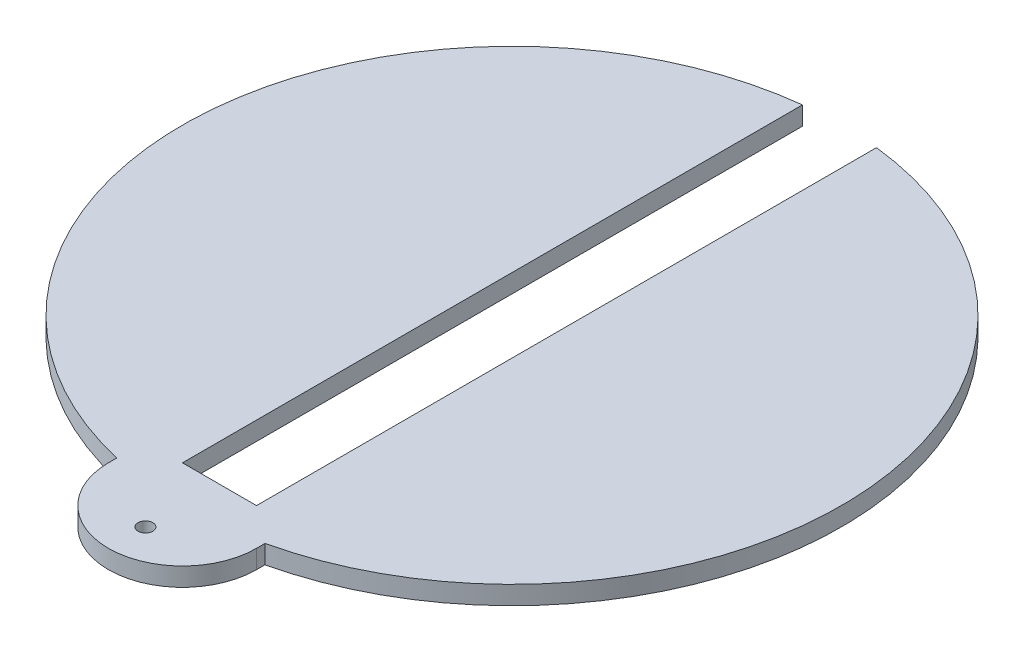
SolidWorks part; units mm, degrees
ref_plane "Front Plane" through (0, 0, 0) normal (0, 0, 1) x (1, 0, 0)
ref_plane "Top Plane" through (0, 0, 0) normal (0, 1, 0) x (1, 0, 0)
ref_plane "Right Plane" through (0, 0, 0) normal (1, 0, 0) x (0, 0, -1)
sketch "Sketch2" plane through (0, 0, 0) normal (0, 1, 0) x (1, 0, 0)
  line L0 (6.35, 56.515) -> (56.515, 56.515)
  line L1 (-56.515, -56.515) -> (-12.7, -56.515)
  line L2 (-56.515, -56.515) -> (-56.515, 56.515)
  line L3 (-56.515, 56.515) -> (-6.35, 56.515)
  line L4 (56.515, -56.515) -> (56.515, 56.515)
  line L5 (-56.515, -56.515) -> (56.515, 56.515) construction
  line L6 (-56.515, 56.515) -> (56.515, -56.515) construction
  line L7 (-6.35, -50.165) -> (6.35, -50.165)
  line L8 (-6.35, -50.165) -> (-6.35, 56.515)
  line L10 (6.35, -50.165) -> (6.35, 56.515)
  line L11 (-6.35, -50.165) -> (6.35, 56.515) construction
  line L12 (-6.35, 56.515) -> (6.35, -50.165) construction
  line L13 (12.7, -56.515) -> (56.515, -56.515)
  arc A0 (-12.7, -56.515) -> (12.7, -56.515) centre (0, -56.515) ccw
  point P0 (0, 0)
  point P6 (0, 3.175)
  dimension "D5" = 12.7
  dimension "D1" = 113.03
  dimension "D2" = 113.03
  dimension "D3" = 12.7
  dimension "D4" = 106.68
extrude "Boss-Extrude1" add sketch "Sketch2" along normal blind 3.175 contours L3 L8 L7 L10 L0 L4 L13 A0 L1 L2
sketch "Sketch3" plane through (0, 3.175, 0) normal (0, 1, 0) x (1, 0, 0)
  line L1 (-6.35, -50.165) -> (6.35, -50.165) construction
  circle A0 centre (0, -62.865) radius 1.27
  dimension "D1" = 2.54
  dimension "D2" = 12.7
extrude "Cut-Extrude1" cut sketch "Sketch3" against normal through all
sketch "Sketch4" plane through (0, 3.175, 0) normal (0, 1, 0) x (1, 0, 0)
  line L0 (-56.515, 56.515) -> (56.515, 56.515)
  line L1 (56.515, 56.515) -> (56.515, -56.515)
  line L3 (56.515, -56.515) -> (12.7, -56.515)
  line L4 (12.7, -56.515) -> (12.7, -55.0695)
  line L5 (-12.7, -55.0695) -> (-12.7, -56.515)
  line L6 (-12.7, -56.515) -> (-56.515, -56.515)
  line L7 (-56.515, -56.515) -> (-56.515, 56.515)
  arc A5 (12.7, -55.0695) -> (-12.7, -55.0695) centre (0, 0) ccw
  line M11 (-56.515, 56.515) -> (-56.515, -56.515)
  line M12 (-56.515, -56.515) -> (-12.7, -56.515)
  line M14 (12.7, -56.515) -> (56.515, -56.515)
  line M15 (56.515, -56.515) -> (56.515, 56.515)
  line M16 (56.515, 56.515) -> (6.35, 56.515)
  line M17 (6.35, 56.515) -> (6.35, -50.165)
  line M19 (-6.35, -50.165) -> (-6.35, 56.515)
  line M20 (-6.35, 56.515) -> (-56.515, 56.515)
extrude "Cut-Extrude2" cut sketch "Sketch4" against normal through all both and the other way through all contours M11 M12 | M19 M20 M11 | M14 M15 | M15 M16 M17 region at (44.1992, 3.175, 43.7821) region at (-44.1992, 3.175, 43.7821) region at (-43.9346, 3.175, -43.8775) region at (43.9346, 3.175, -43.8775)
